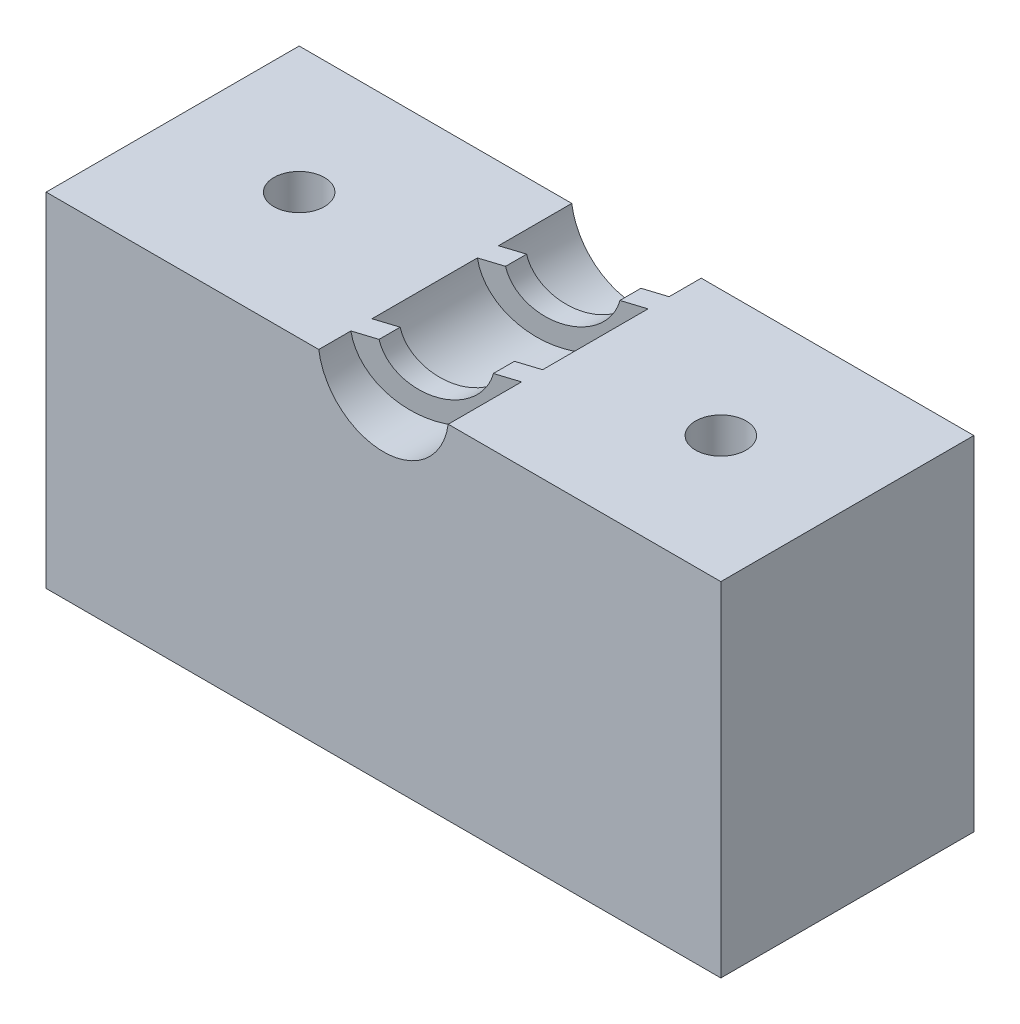
SolidWorks part; units mm, degrees
ref_plane "前视基准面" through (0, 0, 0) normal (0, 0, 1) x (1, 0, 0)
ref_plane "上视基准面" through (0, 0, 0) normal (0, 1, 0) x (1, 0, 0)
ref_plane "右视基准面" through (0, 0, 0) normal (1, 0, 0) x (0, 0, -1)
other "Configuration Table"
sketch "草图1" plane through (0, 0, 0) normal (0, 0, 1) x (1, 0, 0)
  line L1 (-8, -8) -> (8, -8)
  line L2 (-8, -8) -> (-8, 8)
  line L3 (-8, 8) -> (8, 8)
  line L4 (8, -8) -> (8, 8)
  line L5 (-8, -8) -> (8, 8) construction
  line L6 (-8, 8) -> (8, -8) construction
  circle A0 centre (0, 0) radius 1.55
  point P0 (0, 0)
  dimension "D3" = 3.1
  dimension "D1" = 16
  dimension "D2" = 16
extrude "凸台-拉伸1" add sketch "草图1" along normal mid plane 6
sketch "草图6" plane through (0, 0, 0) normal (0, 1, 0) x (1, 0, 0)
  line L0 (-1.55, -3) -> (1.55, -3) construction
  line L1 (1.55, 3) -> (-1.55, 3) construction
  line L2 (-1.55, -3) -> (1.55, -3)
  line L3 (1.55, 3) -> (-1.55, 3)
  line L4 (-1.55, 3) -> (-1.55, -3)
  line L5 (1.55, -3) -> (1.55, 3)
  line L6 (-1.55, 0.7565) -> (1.55, 1.7435)
  line L7 (1.55, 1.7435) -> (1.55, 2.2435)
  line L8 (1.55, 2.2435) -> (-1.55, 1.2565)
  line L9 (-1.55, -1.7435) -> (1.55, -0.7565)
  line L10 (-1.55, -2.2435) -> (1.55, -1.2565)
  line L11 (-2.0945, -0.6668) -> (3.135, 0.9981) construction
  line L12 (-3.1004, 0) -> (4.2723, 0) construction
  dimension "D1" = 2.5
  dimension "D2" = 0.5
  dimension "D3" = 0.5
  dimension "D4" = 17.66
extrude "凸台-拉伸2" add sketch "草图6" against normal up to surface (8 mm away) contours L4 L10 L5 L9 | L5 L8 L4 L6 region at (0, 0, 1.5) region at (0, 0, -1.5) up to face at (0, -8, 0)
sketch "草图7" plane through (0, 0, 0) normal (0, 0, 1) x (1, 0, 0)
  line L0 (0, 0) -> (-1.0279, -0.2141)
  line L1 (0, 0) -> (1.0279, -0.2141)
  line L2 (-1.0279, -0.2141) -> (-8, -0.2141)
  line L3 (1.0279, -0.2141) -> (8, -0.2141)
  line L6 (8, -8) -> (8, 8)
  line L7 (-8, -8) -> (8, -8)
  line L8 (-8, 8) -> (-8, -8)
  line L9 (8, 8) -> (-8, 8)
  line L10 (8, -8) -> (8, 8)
  line L11 (-8, -8) -> (8, -8)
  line L12 (-8, 8) -> (-8, -8)
  line L13 (8, 8) -> (-8, 8)
  circle A0 centre (0, 0) radius 1.05
  dimension "D1" = 2.1
  dimension "D2" = 0
  dimension "D3" = 156.47
extrude "切除-拉伸2" cut sketch "草图7" against normal through all both and the other way through all contours A0 L3 L10 L13 L12 L2 | L1 A0 L0 | L0 A0 L1 region at (0, -0.5019, 0) region at (0, 0.3858, 0) region at (0, 3.953, 0)
sketch "草图8" plane through (0, 0, 0) normal (0, 1, 0) x (1, 0, 0)
  line L0 (0, 5.5834) -> (0, -5.0797) construction
  circle A0 centre (-5, 0) radius 0.6
  circle A1 centre (5, 0) radius 0.6
  dimension "D2" = 1.2
  dimension "D3" = 10
extrude "切除-拉伸3" cut sketch "草图8" against normal through all
sketch "草图9" plane through (0, -8, 0) normal (0, -1, 0) x (1, 0, 0)
  line L4 (-8, -3) -> (8, -3)
  line L5 (8, -3) -> (8, 3)
  line L6 (8, 3) -> (-8, 3)
  line L7 (-8, 3) -> (-8, -3)
  line L8 (-8, -3) -> (8, -3)
  line L9 (8, -3) -> (8, 3)
  line L10 (8, 3) -> (-8, 3)
  line L11 (-8, 3) -> (-8, -3)
  circle A0 centre (-5, 0) radius 0.6 construction
  circle A1 centre (5, 0) radius 0.6 construction
  circle A2 centre (-5, 0) radius 0.6
  circle A3 centre (5, 0) radius 0.6
  dimension "D1" = 0
extrude "凸台-拉伸3" add sketch "草图9" along normal offset from surface (0.355 mm away) 0.6
equation "\"x\"=0.8094"
